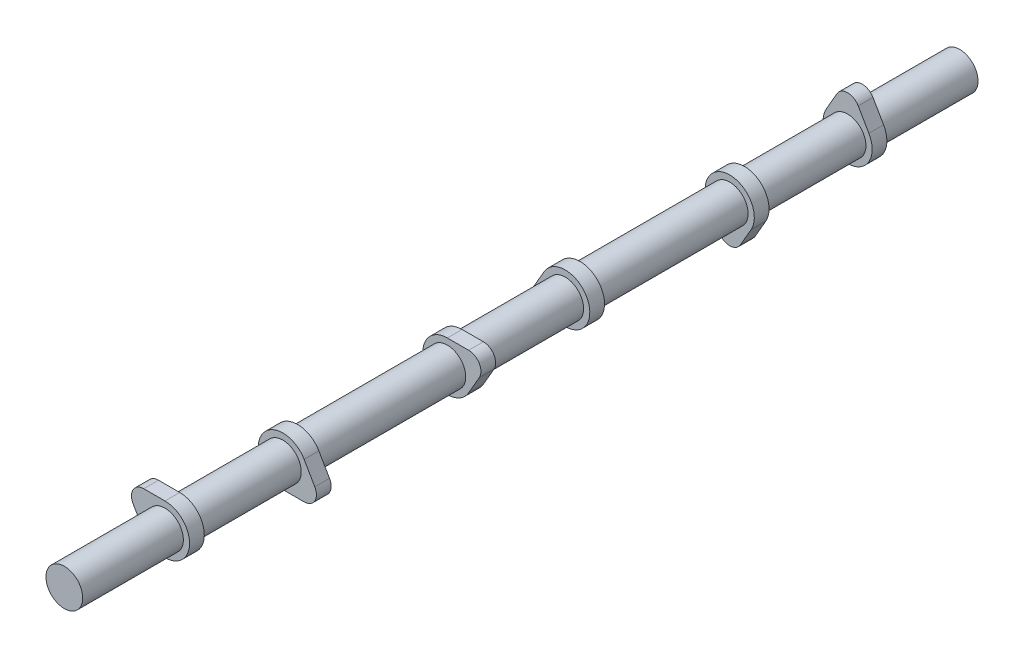
SolidWorks part; units mm, degrees
material "Plain Carbon Steel"
ref_plane "Front Plane" through (0, 0, 0) normal (0, 0, 1) x (1, 0, 0)
ref_plane "Top Plane" through (0, 0, 0) normal (0, 1, 0) x (1, 0, 0)
ref_plane "Right Plane" through (0, 0, 0) normal (1, 0, 0) x (0, 0, -1)
sketch "Sketch1" plane through (0, 0, 0) normal (0, 0, 1) x (1, 0, 0)
  line L0 (-5.4993, 15.875) -> (-10.9985, 6.35)
  line L1 (5.4993, 15.875) -> (10.9985, 6.35)
  arc A0 (-10.9985, 6.35) -> (10.9985, 6.35) centre (0, 0) ccw
  arc A1 (5.4993, 15.875) -> (-5.4993, 15.875) centre (0, 12.7) ccw
  point P9 (0, 0)
  dimension "D1" = 25.4
  dimension "D2" = 12.7
  dimension "D3" = 12.7
extrude "Boss-Extrude1" add sketch "Sketch1" along normal blind 7.62
ref_axis "Axis1" through (0, 0, 285.0601) along (0, 0, -1)
move or copy body "Body-Move/Copy1" bodies to move or copy 101 copy yes number of copies 1 translate (0, 0, 60.96)
move or copy body "Body-Move/Copy2" bodies to move or copy 102 copy no rotation origin (0, 0, 0) rotation axis (0, 0, 1) rotation angle 180
sketch "Sketch2" plane through (0, 0, 0) normal (0, 0, 1) x (1, 0, 0)
  circle A0 centre (0, 0) radius 9.5
  dimension "D1" = 19
extrude "Boss-Extrude2" add sketch "Sketch2" along normal blind 146.05 from offset 25.4 contours A0 offset against normal yes
pattern_linear "LPattern1" count 3 spacing 146.05 along (0, 0, 1) of bodies 104
move or copy body "Body-Move/Copy3" bodies to move or copy 105 copy no rotation origin (0, 0, 0) rotation axis (0, 0, 1) rotation angle 120
move or copy body "Body-Move/Copy4" bodies to move or copy 106 copy no rotation origin (0, 0, 0) rotation axis (0, 0, -1) rotation angle 120
sketch "Sketch3" plane through (0, 0, -25.4) normal (0, 0, -1) x (-1, 0, 0)
  circle A1 centre (0, 0) radius 9.5
  circle A2 centre (0, 0) radius 9.5
  dimension "D1" = 0
extrude "Boss-Extrude3" add sketch "Sketch3" along normal blind 24.94
combine bodies "Combine1" operation type add bodies to combine 109 107 108
